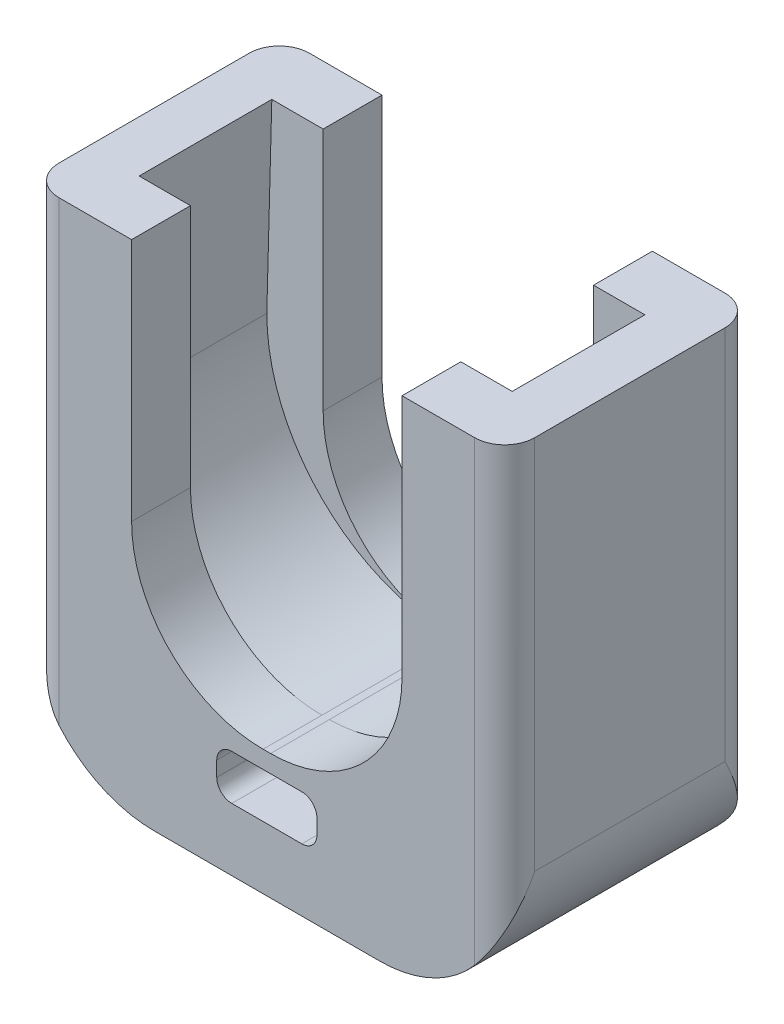
SolidWorks part; units mm, degrees
material "ABS"
ref_plane "Front Plane" through (0, 0, 0) normal (0, 0, 1) x (1, 0, 0)
ref_plane "Top Plane" through (0, 0, 0) normal (0, 1, 0) x (1, 0, 0)
ref_plane "Right Plane" through (0, 0, 0) normal (1, 0, 0) x (0, 0, -1)
sketch "Sketch1" plane through (0, 0, 0) normal (0, 1, 0) x (1, 0, 0)
  line L1 (0, 0) -> (24.13, 0)
  line L2 (0, 0) -> (0, 12.7)
  line L3 (0, 12.7) -> (24.13, 12.7)
  line L4 (24.13, 0) -> (24.13, 12.7)
  dimension "D1" = 24.13
  dimension "D2" = 12.7
extrude "Boss-Extrude1" add sketch "Sketch1" along normal blind 25.4
sketch "Sketch2" plane through (0, 25.4, 0) normal (0, 1, 0) x (1, 0, 0)
  line L0 (0, 12.7) -> (0, 0) construction
  line L1 (2.3495, 2.9845) -> (5.207, 2.9845)
  line L2 (2.3495, 2.9845) -> (2.3495, 9.7155)
  line L3 (2.3495, 9.7155) -> (5.207, 9.7155)
  line L4 (21.7805, 2.9845) -> (21.7805, 9.7155)
  line L5 (0, 0) -> (24.13, 0) construction
  line L6 (5.207, 12.7) -> (18.923, 12.7)
  line L7 (5.207, 12.7) -> (5.207, 9.7155)
  line L8 (5.207, 0) -> (18.923, 0)
  line L9 (18.923, 12.7) -> (18.923, 9.7155)
  line L10 (24.13, 12.7) -> (0, 12.7) construction
  line L11 (5.207, 2.9845) -> (5.207, 0)
  line L12 (18.923, 2.9845) -> (18.923, 0)
  line L13 (18.923, 9.7155) -> (21.7805, 9.7155)
  line L14 (18.923, 2.9845) -> (21.7805, 2.9845)
  point P6 (2.3495, 6.35)
  point P7 (0, 6.35)
  point P24 (12.065, 12.7)
  point P25 (12.065, 12.7)
  dimension "D1" = 6.731
  dimension "D2" = 19.431
  dimension "D3" = 13.716
extrude "Cut-Extrude2" cut sketch "Sketch2" against normal blind 19.05
fillet "Fillet1" radius 9.525 2 edges at (21.7805, 6.35, -6.35) (2.3495, 6.35, -6.35)
fillet "Fillet2" radius 6.6675 4 edges at (5.207, 9.0728, -11.2077) (18.923, 9.0728, -11.2078) (18.923, 9.0728, -1.4922) (5.207, 9.0728, -1.4923)
ref_plane "Plane1" through (0, 0, -6.35) normal (0, 0, 1) x (1, 0, 0)
sketch "Sketch3" plane through (0, 0, -6.35) normal (0, 0, 1) x (1, 0, 0)
  line L0 (21.7805, 25.4) -> (21.5265, 25.4)
  line L1 (18.923, 25.4) -> (21.7805, 25.4) construction
  line L2 (21.5265, 25.4) -> (21.7805, 15.875)
  line L3 (21.7805, 15.875) -> (21.7805, 25.4) construction
  line L4 (21.7805, 15.875) -> (21.7805, 25.4)
  line L5 (2.3495, 25.4) -> (2.6035, 25.4)
  line L6 (2.3495, 25.4) -> (5.207, 25.4) construction
  line L7 (2.6035, 25.4) -> (2.3495, 15.875)
  line L8 (2.3495, 15.875) -> (2.3495, 25.4)
  arc A0 (12.2555, 6.35) -> (21.7805, 15.875) centre (12.2555, 15.875) ccw construction
  dimension "D1" = 0.254
extrude "Boss-Extrude2" add sketch "Sketch3" along normal mid plane 6.731
sketch "Sketch4" plane through (0, 0, 0) normal (0, 0, 1) x (1, 0, 0)
  line L0 (0, 0) -> (24.13, 0) construction
  line L1 (9.525, 5.461) -> (14.605, 5.461)
  line L2 (9.525, 5.461) -> (9.525, 3.175)
  line L3 (9.525, 3.175) -> (14.605, 3.175)
  line L4 (14.605, 5.461) -> (14.605, 3.175)
  point P4 (12.065, 3.175)
  point P7 (12.065, 0)
  dimension "D1" = 5.08
  dimension "D2" = 2.286
  dimension "D3" = 3.175
extrude "Cut-Extrude3" cut sketch "Sketch4" against normal up to next and the other way through all
fillet "Fillet3" radius 0.762 4 edges at (9.525, 3.175, -6.35) (14.605, 3.175, -6.35) (14.605, 5.461, -6.35) (9.525, 5.461, -6.35)
fillet "Fillet4" radius 1.524 4 edges at (0, 12.7, -12.7) (24.13, 12.7, -12.7) (24.13, 12.7, 0) (0, 12.7, 0)
fillet "Fillet5" radius 6.35 2 edges at (24.13, 0, -6.35) (0, 0, -6.35) tangent propagation no
